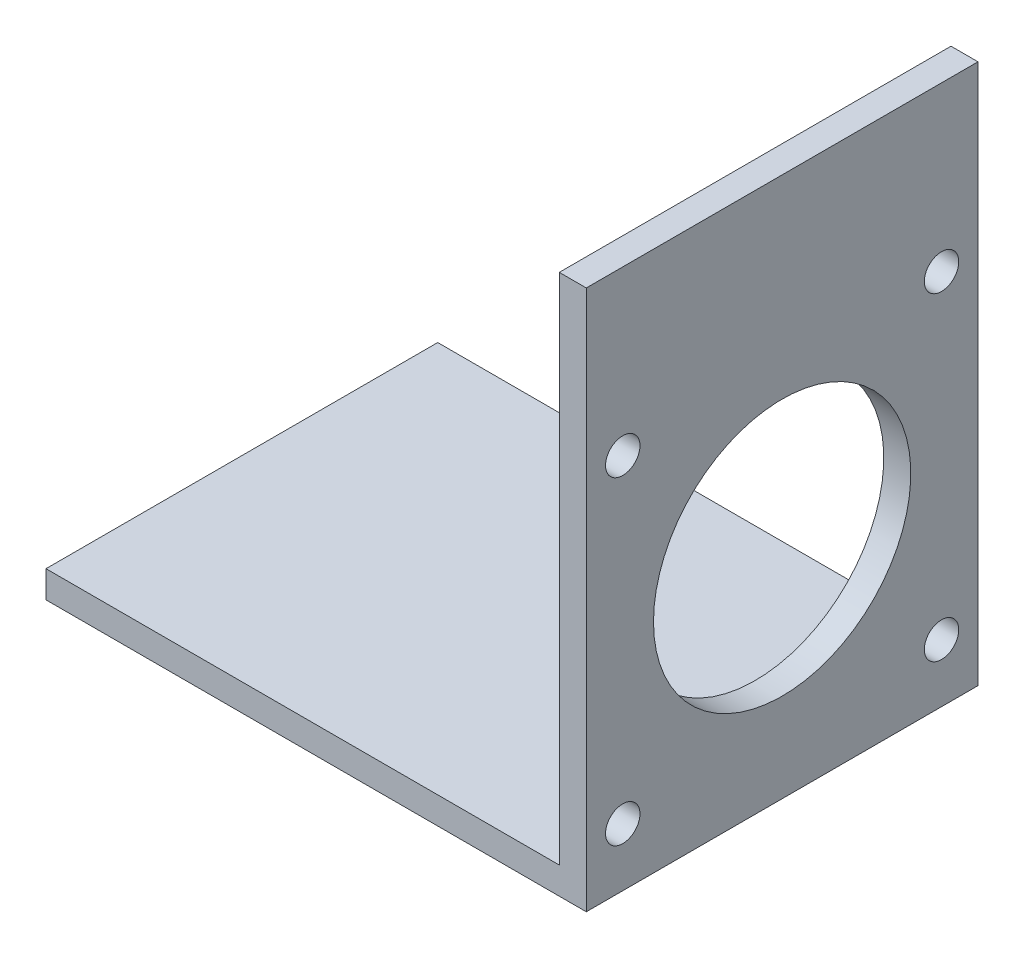
SolidWorks part; units mm, degrees
ref_plane "Front Plane" through (0, 0, 0) normal (0, 0, 1) x (1, 0, 0)
ref_plane "Top Plane" through (0, 0, 0) normal (0, 1, 0) x (1, 0, 0)
ref_plane "Right Plane" through (0, 0, 0) normal (1, 0, 0) x (0, 0, -1)
sketch "Sketch1" plane through (0, 0, 0) normal (0, 1, 0) x (1, 0, 0)
  line L0 (76, 58) -> (76, 0)
  line L1 (0, 0) -> (80, 0)
  line L2 (0, 0) -> (0, 58)
  line L3 (0, 58) -> (80, 58)
  line L4 (80, 0) -> (80, 58)
  dimension "D1" = 80
  dimension "D2" = 58
  dimension "D3" = 4
extrude "Boss-Extrude1" add sketch "Sketch1" along normal blind 4 contours L3 L2 L1 L0 | L1 L4 L3 L0 region at (78, 0, -29) region at (38, 0, -29)
extrude "Boss-Extrude2" add sketch "Sketch1<3>" along normal blind 80 contours L1 L4 L3 L0 region at (78, 0, -29)
sketch "Sketch1<3>" plane through (0, 0, 0) normal (0, 1, 0) x (1, 0, 0) same geometry as "Sketch1"
sketch "Sketch3" plane through (76, 0, 0) normal (-1, 0, 0) x (0, 0, 1)
  line L1 (-57.2, 60.4) -> (-0.8, 60.4)
  line L2 (-57.2, 60.4) -> (-57.2, 4)
  line L3 (-57.2, 4) -> (-0.8, 4)
  line L4 (-0.8, 60.4) -> (-0.8, 4)
  line L5 (0, 4) -> (-58, 4) construction
  line L6 (0, 4) -> (-58, 4)
  line L7 (-58, 80) -> (-58, 4) construction
  line L8 (-29, 60.4) -> (-29, 4) construction
  line L9 (-57.2, 32.2) -> (-0.8, 32.2) construction
  circle A0 centre (-52.6, 55.8) radius 2.55
  circle A1 centre (-5.4, 55.8) radius 2.55
  circle A2 centre (-52.6, 8.6) radius 2.55
  circle A3 centre (-5.4, 8.6) radius 2.55
  circle A4 centre (-29, 32.2) radius 19.05
  dimension "D4" = 5.1
  dimension "D7" = 38.1
  dimension "D1" = 56.4
  dimension "D2" = 56.4
  dimension "D3" = 0.8
  dimension "D5" = 4.6
  dimension "D6" = 4.6
extrude "Cut-Extrude1" cut sketch "Sketch3" against normal blind 80 contours A4 | A1 | A0 | A2 | A3 region at (76, 55.8, -52.6) region at (76, 55.8, -5.4) region at (76, 8.6, -52.6) region at (76, 8.6, -5.4) region at (76, 32.2, -29)
